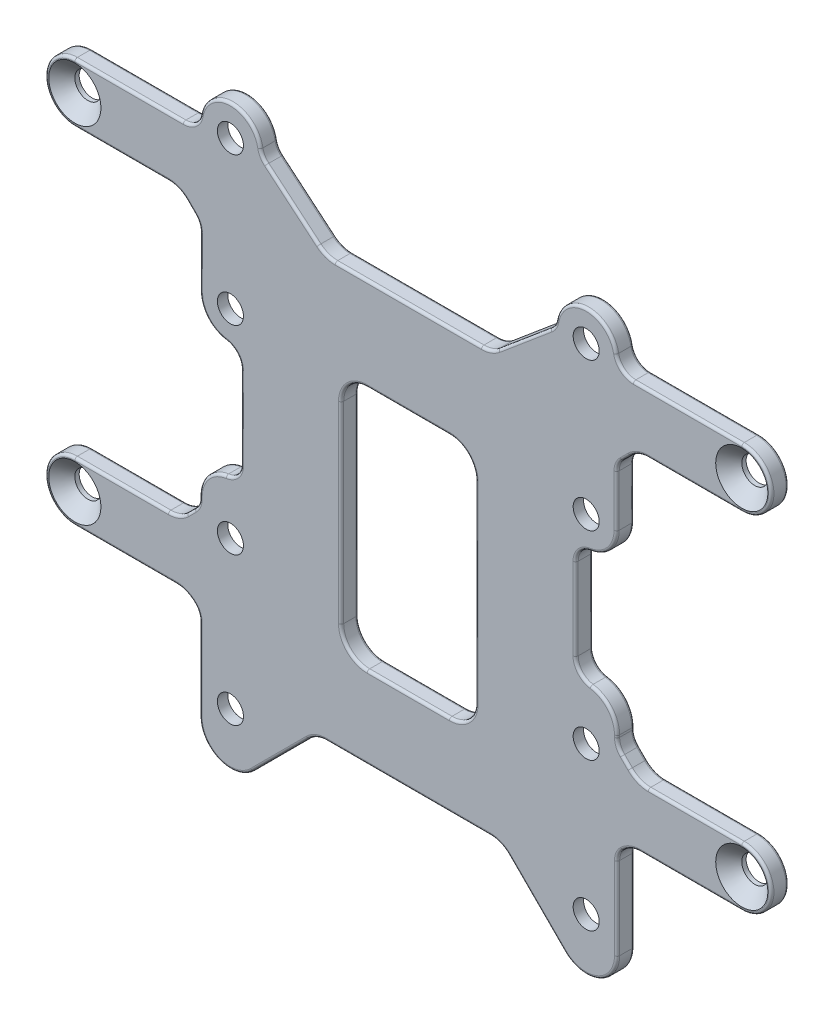
SolidWorks part; units mm, degrees
ref_plane "前视基准面" through (0, 0, 0) normal (0, 0, 1) x (1, 0, 0)
ref_plane "上视基准面" through (0, 0, 0) normal (0, 1, 0) x (1, 0, 0)
ref_plane "右视基准面" through (0, 0, 0) normal (1, 0, 0) x (0, 0, -1)
sketch "草图1" plane through (0, 0, 0) normal (0, 0, 1) x (1, 0, 0)
  line L0 (0, 3.4) -> (-76.7347, 3.4)
  line L1 (-10.7579, -36.3347) -> (0, -36.3347) construction
  line L2 (-18.2387, -30.0965) -> (-12.8792, -35.456) construction
  line L3 (-19.1173, -11.7595) -> (-19.1173, -27.9752) construction
  line L4 (-12.8792, -4.2787) -> (-18.2387, -9.6382) construction
  line L5 (0, -3.4) -> (-10.7579, -3.4) construction
  line L6 (-10.7579, -36.3347) -> (0, -36.3347)
  line L7 (-18.2387, -30.0965) -> (-12.8792, -35.456)
  line L8 (-19.1173, -11.7595) -> (-19.1173, -27.9752)
  line L9 (-12.8792, -4.2787) -> (-18.2387, -9.6382)
  line L10 (0, -3.4) -> (-10.7579, -3.4)
  line L11 (0, -43.1347) -> (-76.7347, -43.1347) construction
  line L12 (0, 0) -> (-76.7347, 0) construction
  line L13 (-38.3673, 0) -> (-38.3673, -74.5917) construction
  line L14 (-65.9768, -36.3347) -> (-76.7347, -36.3347)
  line L15 (-58.496, -30.0965) -> (-63.8555, -35.456)
  line L16 (-57.6173, -11.7595) -> (-57.6173, -27.9752)
  line L17 (-63.8555, -4.2787) -> (-58.496, -9.6382)
  line L18 (-76.7347, -3.4) -> (-65.9768, -3.4)
  line L19 (-13.7579, -44.0134) -> (-19.804, -50.0595)
  line L20 (-20.6827, -52.1809) -> (-20.6827, -60.5911)
  line L21 (-26.9254, -66.8338) -> (-49.8093, -66.8338)
  line L22 (-21.5614, -62.7124) -> (-24.804, -65.9551)
  line L23 (0, -43.1347) -> (-11.6365, -43.1347)
  line L24 (-55.1733, -62.7124) -> (-51.9306, -65.9551)
  line L25 (-56.052, -52.1809) -> (-56.052, -60.5911)
  line L26 (-62.9768, -44.0134) -> (-56.9306, -50.0595)
  line L27 (-76.7347, -43.1347) -> (-65.0981, -43.1347)
  arc A2 (-12.8792, -35.456) -> (-10.7579, -36.3347) centre (-10.7579, -33.3347) ccw construction
  arc A3 (-19.1173, -27.9752) -> (-18.2387, -30.0965) centre (-16.1173, -27.9752) ccw construction
  arc A4 (-18.2387, -9.6382) -> (-19.1173, -11.7595) centre (-16.1173, -11.7595) ccw construction
  arc A5 (-10.7579, -3.4) -> (-12.8792, -4.2787) centre (-10.7579, -6.4) ccw construction
  arc A6 (-12.8792, -35.456) -> (-10.7579, -36.3347) centre (-10.7579, -33.3347) ccw
  arc A7 (-19.1173, -27.9752) -> (-18.2387, -30.0965) centre (-16.1173, -27.9752) ccw
  arc A8 (-18.2387, -9.6382) -> (-19.1173, -11.7595) centre (-16.1173, -11.7595) ccw
  arc A9 (-10.7579, -3.4) -> (-12.8792, -4.2787) centre (-10.7579, -6.4) ccw
  arc A10 (0, -36.3347) -> (0, -43.1347) centre (0, -39.7347) cw
  arc A11 (2.6062, -41.9182) -> (0, -36.3347) centre (0, -39.7347) ccw construction
  arc A12 (-76.7347, -36.3347) -> (-76.7347, -43.1347) centre (-76.7347, -39.7347) ccw
  arc A13 (-57.6173, -27.9752) -> (-58.496, -30.0965) centre (-60.6173, -27.9752) cw
  arc A14 (-58.496, -9.6382) -> (-57.6173, -11.7595) centre (-60.6173, -11.7595) cw
  arc A15 (-65.9768, -3.4) -> (-63.8555, -4.2787) centre (-65.9768, -6.4) cw
  arc A16 (-76.7347, 3.4) -> (-76.7347, -3.4) centre (-76.7347, 0) ccw
  arc A17 (-13.7579, -44.0134) -> (-11.6365, -43.1347) centre (-11.6365, -46.1347) cw
  arc A18 (-19.804, -50.0595) -> (-20.6827, -52.1809) centre (-17.6827, -52.1809) ccw
  arc A19 (-21.5614, -62.7124) -> (-20.6827, -60.5911) centre (-23.6827, -60.5911) ccw
  arc A20 (-24.804, -65.9551) -> (-26.9254, -66.8338) centre (-26.9254, -63.8338) cw
  arc A21 (-51.9306, -65.9551) -> (-49.8093, -66.8338) centre (-49.8093, -63.8338) ccw
  arc A22 (-56.9306, -50.0595) -> (-56.052, -52.1809) centre (-59.052, -52.1809) cw
  arc A23 (-63.8555, -35.456) -> (-65.9768, -36.3347) centre (-65.9768, -33.3347) cw
  arc A24 (-62.9768, -44.0134) -> (-65.0981, -43.1347) centre (-65.0981, -46.1347) ccw
  arc A25 (-55.1733, -62.7124) -> (-56.052, -60.5911) centre (-53.052, -60.5911) cw
  circle A26 centre (-76.7347, -39.7347) radius 1.5 construction
  circle A27 centre (-76.7347, 0) radius 1.5 construction
  circle A28 centre (0, -39.7347) radius 1.5 construction
  circle A29 centre (0, 0) radius 1.5 construction
  circle A30 centre (-76.7347, -39.7347) radius 1.5
  circle A31 centre (-76.7347, 0) radius 1.5
  circle A32 centre (0, -39.7347) radius 1.5
  circle A33 centre (0, 0) radius 1.5
  arc A34 (0, 3.4) -> (0, -3.4) centre (0, 0) cw
  point P22 (-38.3673, 0)
  point P28 (-20.6827, -66.8338)
  point P37 (-38.3673, -43.1347)
  point P52 (-38.3673, 3.4)
  point P55 (-12.8792, -43.1347)
  point P60 (-20.6827, -61.8338)
  point P63 (-25.6827, -66.8338)
  point P65 (-38.3673, -66.8338)
  point P68 (-56.052, -61.8338)
  point P74 (-63.8555, -43.1347)
  dimension "D2" = 3
  dimension "D1" = 135
extrude "凸台-拉伸1" add sketch "草图1" along normal blind 2
sketch "草图2" plane through (0, 0, 2) normal (0, 0, 1) x (1, 0, 0)
  line L0 (-38.3673, 3.2056) -> (-38.3673, 15.4906) construction
  line L2 (0, 3.4) -> (-76.7347, 3.4) construction
  line L3 (-65.9768, -36.3347) -> (-76.7347, -36.3347) construction
  line L4 (-58.8347, 4.45) -> (-17.9, 4.45) construction
  line L5 (-58.8347, 4.45) -> (-58.8347, -12.55) construction
  line L6 (-58.8347, -12.55) -> (-17.9, -12.55) construction
  line L7 (-17.9, 4.45) -> (-17.9, -12.55) construction
  line L8 (-58.8347, 4.45) -> (-17.9, -12.55) construction
  line L9 (-58.8347, -12.55) -> (-17.9, 4.45) construction
  line L10 (-58.8347, -35.4147) -> (-17.9, -35.4147) construction
  line L11 (-58.8347, -35.4147) -> (-58.8347, -52.4147) construction
  line L12 (-58.8347, -52.4147) -> (-17.9, -52.4147) construction
  line L13 (-17.9, -35.4147) -> (-17.9, -52.4147) construction
  line L14 (-58.8347, -35.4147) -> (-17.9, -52.4147) construction
  line L15 (-58.8347, -52.4147) -> (-17.9, -35.4147) construction
  circle A0 centre (-58.8347, 4.45) radius 1.5
  circle A1 centre (-58.8347, -12.55) radius 1.5
  circle A2 centre (-17.9, 4.45) radius 1.5
  circle A3 centre (-17.9, -12.55) radius 1.5
  circle A4 centre (-58.8347, 4.45) radius 3.5
  circle A5 centre (-17.9, 4.45) radius 3.5
  circle A6 centre (-17.9, -12.55) radius 3.5
  circle A7 centre (-58.8347, -12.55) radius 3.5
  circle A8 centre (-58.8347, -35.4147) radius 1.5
  circle A9 centre (-17.9, -35.4147) radius 1.5
  circle A10 centre (-17.9, -52.4147) radius 1.5
  circle A11 centre (-58.8347, -52.4147) radius 1.5
  circle A12 centre (-58.8347, -35.4147) radius 3.5
  circle A13 centre (-17.9, -35.4147) radius 3.5
  circle A14 centre (-17.9, -52.4147) radius 3.5
  circle A15 centre (-58.8347, -52.4147) radius 3.5
  point P1 (-38.3673, 3.4)
  point P6 (-38.3673, -4.05)
  point P18 (-38.3673, -43.9147)
  dimension "D3" = 3
  dimension "D5" = 7
  dimension "D8" = 0.92
  dimension "D1" = 40.9347
  dimension "D2" = 17
  dimension "D4" = 1.05
  dimension "D6" = 40.9347
  dimension "D7" = 17
extrude "凸台-拉伸2" add sketch "草图2" against normal up to surface (2 mm away) up to face at (1.5, -39.7347, 0)
fillet "圆角1" radius 2 12 edges at (-57.6173, -15.8315, 1) (-59.0759, -9.0583, 1) (-55.4959, 3.4, 1) (-62.1735, 3.4, 1) (-14.5612, 3.4, 1) (-21.2388, 3.4, 1) (-17.6588, -9.0583, 1) (-19.1173, -15.8315, 1) (-20.6827, -54.5375, 1) (-56.052, -54.5375, 1) (-57.966, -49.0242, 1) (-18.7687, -49.0242, 1)
sketch "草图3" plane through (0, 0, 2) normal (0, 0, 1) x (1, 0, 0)
  line L0 (-38.3673, -199996.7944) -> (-38.3673, 200015.4906) construction
  line L1 (-38.3673, -199996.7944) -> (-38.3673, 200015.4906)
  line L2 (-58.8347, -12.55) -> (-17.9, -12.55) construction
  line L3 (-43.0995, -12.55) -> (-33.6352, -12.55)
  line L4 (-46.0995, -15.55) -> (-46.0995, -37.7035)
  line L5 (-43.0995, -40.7035) -> (-33.6352, -40.7035)
  line L6 (-30.6352, -15.55) -> (-30.6352, -37.7035)
  line L7 (-46.0995, -12.55) -> (-30.6352, -40.7035) construction
  line L8 (-46.0995, -40.7035) -> (-30.6352, -12.55) construction
  line L9 (-58.8347, -52.4147) -> (-17.9, -35.4147) construction
  circle A0 centre (-58.8347, -52.4147) radius 1.5 construction
  circle A1 centre (-17.9, -52.4147) radius 1.5 construction
  circle A2 centre (-17.9, -35.4147) radius 1.5 construction
  circle A3 centre (-58.8347, -35.4147) radius 1.5 construction
  circle A4 centre (-58.8347, -12.55) radius 1.5 construction
  circle A5 centre (-17.9, -12.55) radius 1.5 construction
  circle A6 centre (-17.9, 4.45) radius 1.5 construction
  circle A7 centre (-58.8347, 4.45) radius 1.5 construction
  circle A8 centre (-58.8347, -52.4147) radius 1.5
  circle A9 centre (-17.9, -52.4147) radius 1.5
  circle A10 centre (-17.9, -35.4147) radius 1.5
  circle A11 centre (-58.8347, -35.4147) radius 1.5
  circle A12 centre (-58.8347, -12.55) radius 1.5
  circle A13 centre (-17.9, -12.55) radius 1.5
  circle A14 centre (-17.9, 4.45) radius 1.5
  circle A15 centre (-58.8347, 4.45) radius 1.5
  arc A16 (-46.0995, -37.7035) -> (-43.0995, -40.7035) centre (-43.0995, -37.7035) ccw
  arc A17 (-33.6352, -40.7035) -> (-30.6352, -37.7035) centre (-33.6352, -37.7035) ccw
  arc A18 (-33.6352, -12.55) -> (-30.6352, -15.55) centre (-33.6352, -15.55) cw
  arc A19 (-43.0995, -12.55) -> (-46.0995, -15.55) centre (-43.0995, -15.55) ccw
  point P26 (-38.3673, -26.6268)
  dimension "D1" = 3
extrude "切除-拉伸1" cut sketch "草图3" against normal through all both and the other way through all
sketch "草图4" plane through (0, 0, 2) normal (0, 0, 1) x (1, 0, 0)
  line L0 (-58.052, -55.8587) -> (-18.6827, -55.8587)
  line L1 (-58.052, -55.8587) -> (-58.052, -67.5153)
  line L2 (-58.052, -67.5153) -> (-18.6827, -67.5153)
  line L3 (-18.6827, -67.5153) -> (-18.6827, -55.8587)
  arc A0 (-56.052, -57.8587) -> (-58.3366, -55.8791) centre (-58.052, -57.8587) ccw construction
  arc A1 (-18.3981, -55.8791) -> (-20.6827, -57.8587) centre (-18.6827, -57.8587) ccw construction
extrude "切除-拉伸2" cut sketch "草图4" against normal through all both and the other way through all
sketch "草图6" plane through (0, 0, 0) normal (0, 0, -1) x (-1, 0, 0)
  line L0 (14.35, -32.9147) -> (14.35, -54.9147) construction
  line L1 (21.45, -54.9147) -> (21.45, -32.9147) construction
  line L2 (62.3847, -54.9147) -> (62.3847, -32.9147) construction
  line L3 (55.2847, -32.9147) -> (55.2847, -54.9147) construction
  line L4 (14.35, -32.9147) -> (14.35, -54.9147)
  line L5 (21.45, -54.9147) -> (21.45, -32.9147)
  line L6 (62.3847, -54.9147) -> (62.3847, -32.9147)
  line L7 (55.2847, -32.9147) -> (55.2847, -54.9147)
  line L8 (62.3347, 4.45) -> (62.3347, -12.55)
  line L9 (55.3873, 5.0545) -> (55.3873, -16.0144)
  line L10 (55.3873, -16.0144) -> (59.3327, -16.0144)
  line L11 (38.3673, 3.4) -> (38.3673, 11.9513) construction
  line L13 (23.3173, 3.4) -> (53.4174, 3.4) construction
  line L14 (21.3474, 5.0545) -> (21.3474, -16.0144)
  line L15 (14.4, 4.45) -> (14.4, -12.55)
  line L16 (21.3474, -16.0144) -> (17.4019, -16.0144)
  arc A0 (14.35, -54.9147) -> (21.45, -54.9147) centre (17.9, -54.9147) ccw construction
  circle A1 centre (17.9, -52.4147) radius 1.5
  circle A2 centre (17.9, -52.4147) radius 1.5
  circle A3 centre (17.9, -35.4147) radius 1.5
  circle A4 centre (17.9, -35.4147) radius 1.5
  circle A5 centre (58.8347, -35.4147) radius 1.5
  circle A6 centre (58.8347, -35.4147) radius 1.5
  circle A7 centre (58.8347, -52.4147) radius 1.5
  circle A8 centre (58.8347, -52.4147) radius 1.5
  arc A9 (21.45, -32.9147) -> (14.35, -32.9147) centre (17.9, -32.9147) ccw construction
  arc A10 (62.3847, -32.9147) -> (55.2847, -32.9147) centre (58.8347, -32.9147) ccw construction
  arc A11 (55.2847, -54.9147) -> (62.3847, -54.9147) centre (58.8347, -54.9147) ccw construction
  arc A12 (14.35, -54.9147) -> (21.45, -54.9147) centre (17.9, -54.9147) ccw
  arc A13 (21.45, -32.9147) -> (14.35, -32.9147) centre (17.9, -32.9147) ccw
  arc A14 (62.3847, -32.9147) -> (55.2847, -32.9147) centre (58.8347, -32.9147) ccw
  arc A15 (55.2847, -54.9147) -> (62.3847, -54.9147) centre (58.8347, -54.9147) ccw
  arc A16 (59.3327, -16.0144) -> (61.1716, -9.9445) centre (58.8347, -12.55) ccw construction
  arc A17 (62.2821, 5.0545) -> (55.3873, 5.0545) centre (58.8347, 4.45) ccw construction
  arc A18 (62.3347, 4.45) -> (55.3873, 5.0545) centre (58.8347, 4.45) ccw
  circle A19 centre (58.8347, 4.45) radius 1.5 construction
  circle A20 centre (58.8347, 4.45) radius 1.5
  circle A21 centre (58.8347, -12.55) radius 1.5 construction
  circle A22 centre (58.8347, -12.55) radius 1.5
  arc A23 (62.3347, -12.55) -> (59.3327, -16.0144) centre (58.8347, -12.55) cw
  arc A24 (14.4, 4.45) -> (21.3474, 5.0545) centre (17.9, 4.45) cw
  arc A25 (14.4, -12.55) -> (17.4019, -16.0144) centre (17.9, -12.55) ccw
  circle A26 centre (17.9, -12.55) radius 1.5
  circle A27 centre (17.9, 4.45) radius 1.5
  point P46 (38.3673, 3.4)
  dimension "D1" = 0
  dimension "D2" = 0
  dimension "D3" = 0
  dimension "D4" = 0
extrude "凸台-拉伸3" add sketch "草图6" against normal up to surface (2 mm away) up to face at (-19.4, -35.4147, 2)
sketch "草图7" plane through (0, 0, 2) normal (0, 0, 1) x (1, 0, 0)
  line L4 (-54.7036, 3.8685) -> (-48.7103, -1.1653)
  line L5 (-46.7808, -1.8681) -> (-29.9539, -1.8681)
  line L6 (-28.0244, -1.1653) -> (-22.031, 3.8685)
  line L7 (-22.031, 3.8685) -> (-54.7036, 3.8685)
  line L8 (-20.4102, -57.4249) -> (-26.8355, -50.9996)
  line L9 (-28.9569, -50.1209) -> (-47.7778, -50.1209)
  line L10 (-49.8991, -50.9996) -> (-56.3245, -57.4249)
  line L11 (-20.4102, -57.4249) -> (-56.3245, -57.4249)
  arc A0 (-21.3222, -55.8587) -> (-14.35, -54.9147) centre (-17.9, -54.9147) ccw construction
  arc A1 (-62.3847, -54.9147) -> (-55.4125, -55.8587) centre (-58.8347, -54.9147) ccw construction
  arc A4 (-55.3873, 5.0545) -> (-53.4174, 3.4) centre (-53.4174, 5.4) ccw construction
  arc A5 (-23.3173, 3.4) -> (-21.3474, 5.0545) centre (-23.3173, 5.4) ccw construction
  arc A6 (-29.9539, -1.8681) -> (-28.0244, -1.1653) centre (-29.9539, 1.1319) ccw
  arc A7 (-48.7103, -1.1653) -> (-46.7808, -1.8681) centre (-46.7808, 1.1319) ccw
  arc A8 (-47.7778, -50.1209) -> (-49.8991, -50.9996) centre (-47.7778, -53.1209) ccw
  arc A9 (-26.8355, -50.9996) -> (-28.9569, -50.1209) centre (-28.9569, -53.1209) ccw
  dimension "D3" = 3
extrude "切除-拉伸3" cut sketch "草图7" against normal through all both and the other way through all
sketch "草图8" plane through (0, 0, 2) normal (0, 0, 1) x (1, 0, 0)
  line L0 (-54.7583, -55.8587) -> (-56.3245, -57.4249)
  line L2 (-54.7583, -55.8587) -> (-56.3245, -55.8587)
  line L3 (-56.3245, -55.8587) -> (-56.3245, -57.4249)
  line L4 (-21.9764, -55.8587) -> (-20.4102, -57.4249)
  line L6 (-21.9764, -55.8587) -> (-20.4102, -55.8587)
  line L7 (-20.4102, -55.8587) -> (-20.4102, -57.4249)
extrude "凸台-拉伸4" add sketch "草图8" against normal up to surface (2 mm away) up to face at (-38.3673, -24.0106, 0)
chamfer "倒角1" distance 1.5 angle 45 4 edges at (1.5, 0, 2) (1.5, -39.7347, 2) (-75.2347, 0, 2) (-75.2347, -39.7347, 2)
sketch "草图9" plane through (0, 0, 0) normal (0, 0, -1) x (-1, 0, 0)
  line L1 (19.2279, 7.25) -> (16.5721, 7.25)
  line L2 (16.1391, 7) -> (14.8112, 4.7)
  line L3 (14.8112, 4.2) -> (16.1391, 1.9)
  line L4 (16.5721, 1.65) -> (19.2279, 1.65)
  line L5 (19.6609, 1.9) -> (20.9888, 4.2)
  line L6 (20.9888, 4.7) -> (19.6609, 7)
  line L7 (57.5068, 1.65) -> (60.1626, 1.65)
  line L8 (60.5956, 1.9) -> (61.9235, 4.2)
  line L9 (61.9235, 4.7) -> (60.5956, 7)
  line L10 (60.1626, 7.25) -> (57.5068, 7.25)
  line L11 (57.0738, 7) -> (55.7459, 4.7)
  line L12 (55.7459, 4.2) -> (57.0738, 1.9)
  line L13 (19.6609, -15.1) -> (20.9888, -12.8)
  line L14 (20.9888, -12.3) -> (19.6609, -10)
  line L15 (19.2279, -9.75) -> (16.5721, -9.75)
  line L16 (16.1391, -10) -> (14.8112, -12.3)
  line L17 (14.8112, -12.8) -> (16.1391, -15.1)
  line L18 (16.5721, -15.35) -> (19.2279, -15.35)
  line L19 (60.5956, -15.1) -> (61.9235, -12.8)
  line L20 (61.9235, -12.3) -> (60.5956, -10)
  line L21 (60.1626, -9.75) -> (57.5068, -9.75)
  line L22 (57.0738, -10) -> (55.7459, -12.3)
  line L23 (55.7459, -12.8) -> (57.0738, -15.1)
  line L24 (57.5068, -15.35) -> (60.1626, -15.35)
  line L25 (16.5721, -38.2147) -> (19.2279, -38.2147)
  line L26 (19.6609, -37.9647) -> (20.9888, -35.6647)
  line L27 (20.9888, -35.1647) -> (19.6609, -32.8647)
  line L28 (19.2279, -32.6147) -> (16.5721, -32.6147)
  line L29 (16.1391, -32.8647) -> (14.8112, -35.1647)
  line L30 (14.8112, -35.6647) -> (16.1391, -37.9647)
  line L31 (19.2279, -49.6147) -> (16.5721, -49.6147)
  line L32 (16.1391, -49.8647) -> (14.8112, -52.1647)
  line L33 (14.8112, -52.6647) -> (16.1391, -54.9647)
  line L34 (16.5721, -55.2147) -> (19.2279, -55.2147)
  line L35 (19.6609, -54.9647) -> (20.9888, -52.6647)
  line L36 (20.9888, -52.1647) -> (19.6609, -49.8647)
  line L37 (60.1626, -32.6147) -> (57.5068, -32.6147)
  line L38 (57.0738, -32.8647) -> (55.7459, -35.1647)
  line L39 (55.7459, -35.6647) -> (57.0738, -37.9647)
  line L40 (57.5068, -38.2147) -> (60.1626, -38.2147)
  line L41 (60.5956, -37.9647) -> (61.9235, -35.6647)
  line L42 (61.9235, -35.1647) -> (60.5956, -32.8647)
  line L43 (60.1626, -49.6147) -> (57.5068, -49.6147)
  line L44 (57.0738, -49.8647) -> (55.7459, -52.1647)
  line L45 (55.7459, -52.6647) -> (57.0738, -54.9647)
  line L46 (57.5068, -55.2147) -> (60.1626, -55.2147)
  line L47 (60.5956, -54.9647) -> (61.9235, -52.6647)
  line L48 (61.9235, -52.1647) -> (60.5956, -49.8647)
  circle A0 centre (17.9, 4.45) radius 2.8 construction
  circle A1 centre (58.8347, 4.45) radius 2.8 construction
  circle A2 centre (17.9, -12.55) radius 2.8 construction
  circle A3 centre (58.8347, -12.55) radius 2.8 construction
  circle A4 centre (17.9, -35.4147) radius 2.8 construction
  circle A5 centre (17.9, -52.4147) radius 2.8 construction
  circle A6 centre (58.8347, -35.4147) radius 2.8 construction
  circle A7 centre (58.8347, -52.4147) radius 2.8 construction
  arc A8 (61.9235, -52.6647) -> (61.9235, -52.1647) centre (61.4905, -52.4147) ccw
  arc A9 (60.1626, -55.2147) -> (60.5956, -54.9647) centre (60.1626, -54.7147) ccw
  arc A10 (57.0738, -54.9647) -> (57.5068, -55.2147) centre (57.5068, -54.7147) ccw
  arc A11 (55.7459, -52.1647) -> (55.7459, -52.6647) centre (56.1789, -52.4147) ccw
  arc A12 (57.5068, -49.6147) -> (57.0738, -49.8647) centre (57.5068, -50.1147) ccw
  arc A13 (60.1626, -49.6147) -> (60.5956, -49.8647) centre (60.1626, -50.1147) cw
  arc A14 (61.9235, -35.6647) -> (61.9235, -35.1647) centre (61.4905, -35.4147) ccw
  arc A15 (60.1626, -38.2147) -> (60.5956, -37.9647) centre (60.1626, -37.7147) ccw
  arc A16 (57.0738, -37.9647) -> (57.5068, -38.2147) centre (57.5068, -37.7147) ccw
  arc A17 (55.7459, -35.1647) -> (55.7459, -35.6647) centre (56.1789, -35.4147) ccw
  arc A18 (57.5068, -32.6147) -> (57.0738, -32.8647) centre (57.5068, -33.1147) ccw
  arc A19 (60.1626, -32.6147) -> (60.5956, -32.8647) centre (60.1626, -33.1147) cw
  arc A20 (20.9888, -52.6647) -> (20.9888, -52.1647) centre (20.5558, -52.4147) ccw
  arc A21 (19.2279, -55.2147) -> (19.6609, -54.9647) centre (19.2279, -54.7147) ccw
  arc A22 (16.1391, -54.9647) -> (16.5721, -55.2147) centre (16.5721, -54.7147) ccw
  arc A23 (14.8112, -52.1647) -> (14.8112, -52.6647) centre (15.2442, -52.4147) ccw
  arc A24 (16.5721, -49.6147) -> (16.1391, -49.8647) centre (16.5721, -50.1147) ccw
  arc A25 (19.2279, -49.6147) -> (19.6609, -49.8647) centre (19.2279, -50.1147) cw
  arc A26 (14.8112, -35.1647) -> (14.8112, -35.6647) centre (15.2442, -35.4147) ccw
  arc A27 (16.5721, -32.6147) -> (16.1391, -32.8647) centre (16.5721, -33.1147) ccw
  arc A28 (19.6609, -32.8647) -> (19.2279, -32.6147) centre (19.2279, -33.1147) ccw
  arc A29 (20.9888, -35.6647) -> (20.9888, -35.1647) centre (20.5558, -35.4147) ccw
  arc A30 (19.2279, -38.2147) -> (19.6609, -37.9647) centre (19.2279, -37.7147) ccw
  arc A31 (16.5721, -38.2147) -> (16.1391, -37.9647) centre (16.5721, -37.7147) cw
  arc A32 (57.0738, -15.1) -> (57.5068, -15.35) centre (57.5068, -14.85) ccw
  arc A33 (55.7459, -12.3) -> (55.7459, -12.8) centre (56.1789, -12.55) ccw
  arc A34 (57.5068, -9.75) -> (57.0738, -10) centre (57.5068, -10.25) ccw
  arc A35 (60.5956, -10) -> (60.1626, -9.75) centre (60.1626, -10.25) ccw
  arc A36 (61.9235, -12.8) -> (61.9235, -12.3) centre (61.4905, -12.55) ccw
  arc A37 (60.5956, -15.1) -> (60.1626, -15.35) centre (60.1626, -14.85) cw
  arc A38 (16.1391, -15.1) -> (16.5721, -15.35) centre (16.5721, -14.85) ccw
  arc A39 (14.8112, -12.3) -> (14.8112, -12.8) centre (15.2442, -12.55) ccw
  arc A40 (16.5721, -9.75) -> (16.1391, -10) centre (16.5721, -10.25) ccw
  arc A41 (19.6609, -10) -> (19.2279, -9.75) centre (19.2279, -10.25) ccw
  arc A42 (20.9888, -12.8) -> (20.9888, -12.3) centre (20.5558, -12.55) ccw
  arc A43 (19.6609, -15.1) -> (19.2279, -15.35) centre (19.2279, -14.85) cw
  arc A44 (55.7459, 4.7) -> (55.7459, 4.2) centre (56.1789, 4.45) ccw
  arc A45 (57.5068, 7.25) -> (57.0738, 7) centre (57.5068, 6.75) ccw
  arc A46 (60.5956, 7) -> (60.1626, 7.25) centre (60.1626, 6.75) ccw
  arc A47 (61.9235, 4.2) -> (61.9235, 4.7) centre (61.4905, 4.45) ccw
  arc A48 (60.1626, 1.65) -> (60.5956, 1.9) centre (60.1626, 2.15) ccw
  arc A49 (57.5068, 1.65) -> (57.0738, 1.9) centre (57.5068, 2.15) cw
  arc A50 (20.9888, 4.2) -> (20.9888, 4.7) centre (20.5558, 4.45) ccw
  arc A51 (19.2279, 1.65) -> (19.6609, 1.9) centre (19.2279, 2.15) ccw
  arc A52 (16.1391, 1.9) -> (16.5721, 1.65) centre (16.5721, 2.15) ccw
  arc A53 (14.8112, 4.7) -> (14.8112, 4.2) centre (15.2442, 4.45) ccw
  arc A54 (16.5721, 7.25) -> (16.1391, 7) centre (16.5721, 6.75) ccw
  arc A55 (19.2279, 7.25) -> (19.6609, 7) centre (19.2279, 6.75) cw
  dimension "D2" = 0.5
  dimension "D1" = 5.6
extrude "切除-拉伸4" cut sketch "草图9" against normal blind 0.8
fillet "圆角3" radius 2 8 edges at (-62.3347, -5.7995, 1) (-14.4, -5.7995, 1) (-18.7233, -29.4615, 1) (-14.35, -33.9852, 1) (-14.35, -44.6055, 1) (-62.3847, -44.6055, 1) (-62.3847, -33.9852, 1) (-58.0114, -29.4615, 1)
fillet "圆角2" radius 0.3 144 edges at (-13.761, -44.0165, 2) (-13.761, -44.0165, 0) (-12.7846, -43.3631, 0) (-12.7846, -43.3631, 2) (-5.8183, -43.1347, 0) (-5.8183, -43.1347, 2) (3.4, -39.7347, 0) (3.4, -39.7347, 2) (-5.3789, -36.3347, 0) (-5.3789, -36.3347, 2) (-11.9059, -36.1063, 0) (-11.9059, -36.1063, 2) (-13.3217, -35.0135, 0) (-13.3217, -35.0135, 2) (-19.1173, -22.7071, 2) (-19.1173, -22.7071, 0) (-18.6288, -16.6843, 0) (-18.6288, -16.6843, 2) (-15.2549, -14.842, 2) (-15.2549, -14.842, 0) (-13.3467, -4.7462, 2) (-13.3467, -4.7462, 0) (-11.9059, -3.6284, 0) (-11.9059, -3.6284, 2) (-5.3789, -3.4, 0) (-5.3789, -3.4, 2) (3.4, 0, 0) (3.4, 0, 2) (-6.2413, 3.4, 0) (-6.2413, 3.4, 2) (-13.769, 3.8685, 0) (-13.769, 3.8685, 2) (-17.9, 7.95, 0) (-17.9, 7.95, 2) (-21.5846, 4.4012, 2) (-21.5846, 4.4012, 0) (-55.1501, 4.4012, 2) (-55.1501, 4.4012, 0) (-58.8347, 7.95, 2) (-58.8347, 7.95, 0) (-62.9657, 3.8685, 2) (-62.9657, 3.8685, 0) (-70.4934, 3.4, 2) (-70.4934, 3.4, 0) (-80.1347, 0, 0) (-80.1347, 0, 2) (-71.3558, -3.4, 0) (-71.3558, -3.4, 2) (-64.8288, -3.6284, 0) (-64.8288, -3.6284, 2) (-63.388, -4.7462, 0) (-63.388, -4.7462, 2) (-61.4798, -14.842, 2) (-61.4798, -14.842, 0) (-58.1059, -16.6843, 2) (-58.1059, -16.6843, 0) (-57.6173, -22.7071, 0) (-57.6173, -22.7071, 2) (-63.413, -35.0135, 2) (-63.413, -35.0135, 0) (-64.8288, -36.1063, 0) (-64.8288, -36.1063, 2) (-71.3558, -36.3347, 0) (-71.3558, -36.3347, 2) (-80.1347, -39.7347, 0) (-80.1347, -39.7347, 2) (-70.9164, -43.1347, 0) (-70.9164, -43.1347, 2) (-63.9501, -43.3631, 0) (-63.9501, -43.3631, 2) (-62.9737, -44.0165, 0) (-62.9737, -44.0165, 2) (-45.2209, -13.4287, 0) (-45.2209, -13.4287, 2) (-38.3673, -12.55, 0) (-38.3673, -12.55, 2) (-31.5138, -13.4287, 0) (-31.5138, -13.4287, 2) (-30.6352, -26.6268, 0) (-30.6352, -26.6268, 2) (-31.5138, -39.8249, 0) (-31.5138, -39.8249, 2) (-38.3673, -40.7035, 0) (-38.3673, -40.7035, 2) (-45.2209, -39.8249, 0) (-45.2209, -39.8249, 2) (-46.0995, -26.6268, 0) (-46.0995, -26.6268, 2) (-14.35, -33.0357, 2) (-14.35, -33.0357, 0) (-15.2186, -30.5882, 0) (-15.2186, -30.5882, 2) (-53.1118, -54.2123, 2) (-53.1118, -54.2123, 0) (-62.3847, -33.0357, 0) (-62.3847, -33.0357, 2) (-61.5161, -30.5882, 2) (-61.5161, -30.5882, 0) (-23.6229, -54.2123, 0) (-23.6229, -54.2123, 2) (-16.5415, -58.1945, 0) (-51.707, 1.3516, 0) (-51.707, 1.3516, 2) (-47.8075, -1.6869, 0) (-47.8075, -1.6869, 2) (-38.3673, -1.8681, 0) (-38.3673, -1.8681, 2) (-28.9272, -1.6869, 0) (-28.9272, -1.6869, 2) (-25.0277, 1.3516, 0) (-25.0277, 1.3516, 2) (-62.3847, -50.1743, 2) (-62.3847, -50.1743, 0) (-14.35, -50.1743, 0) (-14.35, -50.1743, 2) (-60.1932, -58.1945, 0) (-14.4, -9.589, 0) (-14.4, -9.589, 2) (-62.3347, -9.589, 2) (-62.3347, -9.589, 0) (-62.4869, -5.8626, 0) (-62.4869, -5.8626, 2) (-14.2478, -5.8626, 2) (-14.2478, -5.8626, 0) (-48.9259, -50.3493, 0) (-48.9259, -50.3493, 2) (-38.3673, -50.1209, 0) (-38.3673, -50.1209, 2) (-27.8088, -50.3493, 0) (-27.8088, -50.3493, 2) (-62.5369, -44.6686, 0) (-62.5369, -44.6686, 2) (-62.5369, -33.9221, 2) (-62.5369, -33.9221, 0) (-58.1067, -28.7309, 0) (-58.1067, -28.7309, 2) (-18.628, -28.7309, 2) (-18.628, -28.7309, 0) (-14.1978, -33.9221, 0) (-14.1978, -33.9221, 2) (-14.1978, -44.6686, 2) (-14.1978, -44.6686, 0)
